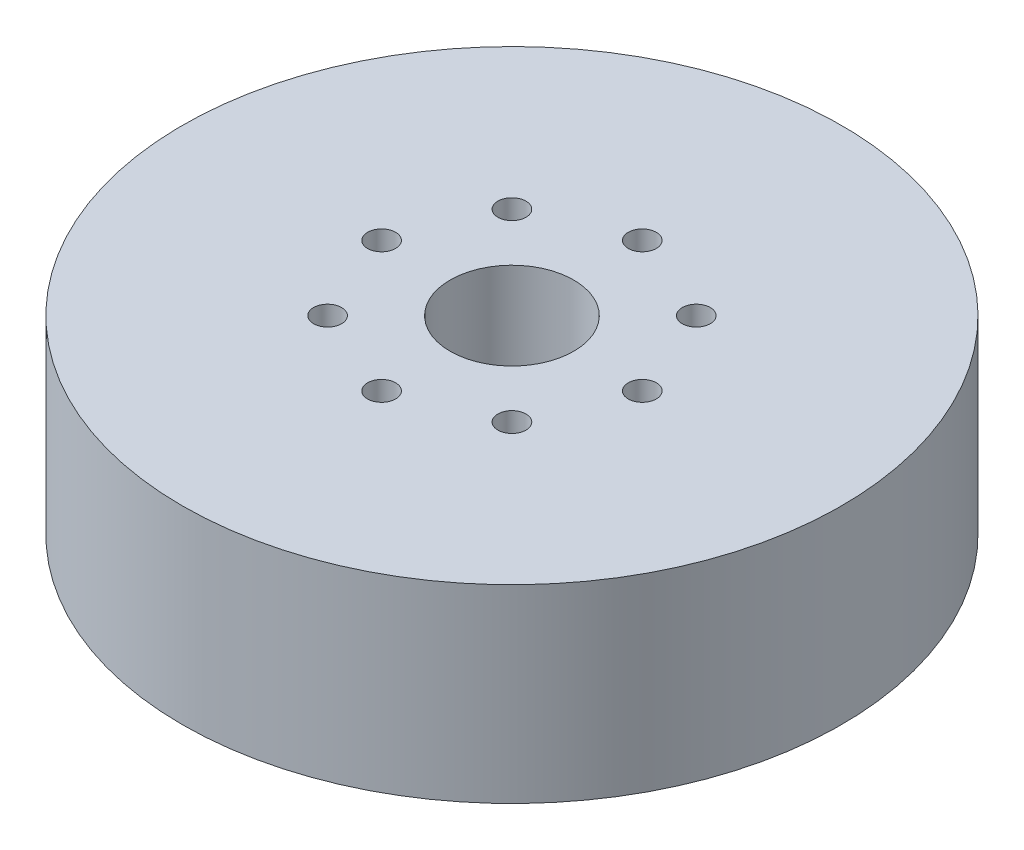
SolidWorks part; units mm, degrees
ref_plane "Front Plane" through (0, 0, 0) normal (0, 0, 1) x (1, 0, 0)
ref_plane "Top Plane" through (0, 0, 0) normal (0, 1, 0) x (1, 0, 0)
ref_plane "Right Plane" through (0, 0, 0) normal (1, 0, 0) x (0, 0, -1)
sketch "Sketch1" plane through (0, 0, 0) normal (0, 1, 0) x (1, 0, 0)
  circle A0 centre (0, 0) radius 40
  dimension "FLANGE_OD" = 80
extrude "Boss-Extrude1" add sketch "Sketch1" along normal blind 23
sketch "Sketch2" plane through (0, 0, 0) normal (0, 1, 0) x (1, 0, 0)
  circle A0 centre (0, 0) radius 7.5
  dimension "BORE_D" = 15
extrude "Cut-Extrude1" cut sketch "Sketch2" along normal through all
sketch "Sketch3" plane through (0, 23, 0) normal (0, 1, 0) x (1, 0, 0)
  circle A0 centre (0, 0) radius 15.8197 construction
  circle A1 centre (-15.8197, 0) radius 1.7039
  dimension "BOLT_D" = 3.4078
  dimension "BOLT_PCD" = 31.6394
extrude "Cut-Extrude2" cut sketch "Sketch3" against normal blind 16.2859
pattern_circular "CirPattern1" count 8 over 360 about axis through (0, 0, 0) along (0, 1, 0) of "Cut-Extrude2"
